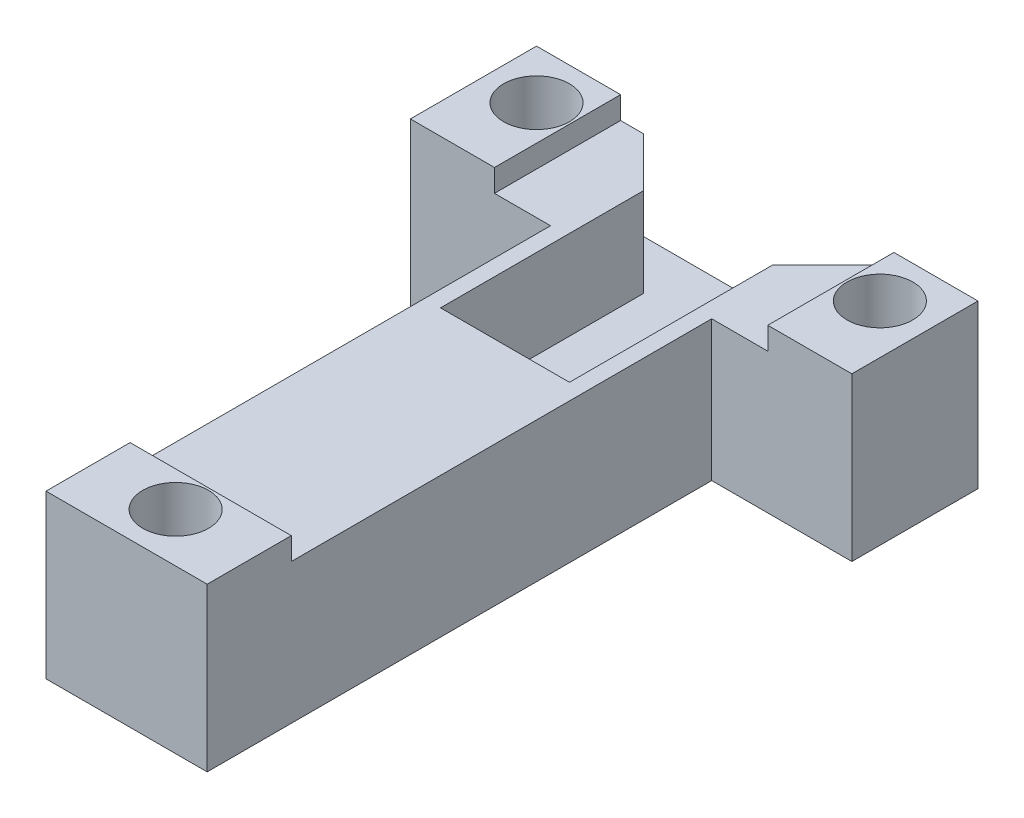
SolidWorks part; units mm, degrees
ref_plane "Front Plane" through (0, 0, 0) normal (0, 0, 1) x (1, 0, 0)
ref_plane "Top Plane" through (0, 0, 0) normal (0, 1, 0) x (1, 0, 0)
ref_plane "Right Plane" through (0, 0, 0) normal (1, 0, 0) x (0, 0, -1)
sketch "Sketch1" plane through (0, 0, 0) normal (0, 1, 0) x (1, 0, 0)
  line L0 (11.5, 45) -> (21.5, 45)
  line L1 (0, 0) -> (11.5, 0)
  line L2 (0, 0) -> (0, 45)
  line L3 (0, 45) -> (11.5, 45)
  line L4 (11.5, 0) -> (11.5, 45)
  line L5 (21.5, 45) -> (21.5, 36)
  line L6 (21.5, 36) -> (11.5, 36)
  line L7 (0, 45) -> (-10, 45)
  line L8 (-10, 45) -> (-10, 36)
  line L9 (-10, 36) -> (0, 36)
  dimension "D3" = 9
  dimension "D1" = 45
  dimension "D2" = 11.5
  dimension "D4" = 10
  dimension "D5" = 10
extrude "Boss-Extrude1" add sketch "Sketch1" along normal blind 10 contours L8 L9 L2 L7 | L6 L5 L0 L4 | L4 L3 L2 L1 region at (16.5, 0, -40.5) region at (-5, 0, -40.5)
sketch "Sketch2" plane through (0, 10, 0) normal (0, 1, 0) x (1, 0, 0)
  line L0 (5.75, 0) -> (5.75, 45) construction
  line L3 (0, 36) -> (11.5, 36) construction
  line L4 (5.75, 36) -> (5.75, 27)
  line L5 (1.15, 27) -> (10.35, 27)
  line L6 (1.15, 27) -> (1.15, 45)
  line L7 (21.5, 45) -> (-10, 45) construction
  line L8 (10.35, 27) -> (10.35, 45)
  line L9 (1.15, 45) -> (10.35, 45)
  line L10 (0, 0) -> (11.5, 0) construction
  line L11 (-10, 45) -> (-10, 36) construction
  line L12 (21.5, 45) -> (21.5, 36) construction
  line L13 (1.15, 41.5) -> (-2.35, 45)
  line L14 (10.35, 41.5) -> (13.85, 45)
  circle A0 centre (5.75, 3.5) radius 2.3495
  circle A1 centre (-6.5, 41.5) radius 2.3495
  circle A2 centre (18, 41.5) radius 2.3495
  point P17 (5.75, 27)
  line M29 (21.5, 45) -> (-10, 45)
  dimension "D1" = 4.699
  dimension "D9" = 4.699
  dimension "D10" = 4.699
  dimension "D2" = 9
  dimension "D3" = 9.2
  dimension "D4" = 3.5
  dimension "D5" = 3.5
  dimension "D6" = 3.5
  dimension "D7" = 3.5
  dimension "D8" = 3.5
  dimension "D11" = 3.5
  dimension "D12" = 3.5
  dimension "D13" = 3.5
  dimension "D14" = 3.5
extrude "Cut-Extrude1" cut sketch "Sketch2" against normal blind 6.35 contours A0 | A2 | L9 L6 L5 L8 | A1 | L13 L6 M29 | L8 L14 M29 region at (1.3521, 10, -34.25) region at (-0.0167, 10, -43.8333) region at (11.5167, 10, -43.8333) region at (5.75, 10, -3.5) region at (-6.5, 10, -41.5) region at (18, 10, -41.5)
sketch "Sketch3" plane through (0, 0, 0) normal (0, -1, 0) x (1, 0, 0)
  line L0 (5.75, 0) -> (5.75, -45) construction
  line L1 (0, 0) -> (11.5, 0) construction
  line L2 (21.5, -45) -> (-10, -45) construction
  circle A0 centre (5.75, -10) radius 2.3495
  circle A1 centre (5.75, -22) radius 2.3495
  dimension "D3" = 4.699
  dimension "D4" = 4.699
  dimension "D1" = 10
  dimension "D2" = 12
extrude "Cut-Extrude2" cut sketch "Sketch3" against normal blind 6.35
sketch "Sketch4" plane through (0, 10, 0) normal (0, 1, 0) x (1, 0, 0)
  line L0 (-4, 36) -> (-4, 45)
  line L1 (-10, 36) -> (0, 36) construction
  line L2 (-2.35, 45) -> (-10, 45) construction
  line L3 (15.5, 36) -> (15.5, 45)
  line L4 (21.5, 36) -> (11.5, 36) construction
  line L5 (21.5, 45) -> (13.85, 45) construction
  line L6 (0, 6) -> (11.5, 6)
  line L7 (0, 0) -> (0, 36) construction
  line L8 (11.5, 0) -> (11.5, 36) construction
  line L9 (0, 0) -> (11.5, 0) construction
  line L10 (-10, 45) -> (-10, 36) construction
  line L11 (21.5, 45) -> (21.5, 36) construction
  circle M4 centre (5.75, 3.5) radius 2.3495
  circle M5 centre (-6.5, 41.5) radius 2.3495
  circle M6 centre (18, 41.5) radius 2.3495
  line M9 (-2.35, 45) -> (-10, 45)
  line M10 (-10, 45) -> (-10, 36)
  line M11 (-10, 36) -> (0, 36)
  line M12 (0, 36) -> (0, 0)
  line M13 (0, 0) -> (11.5, 0)
  line M14 (11.5, 0) -> (11.5, 36)
  line M15 (11.5, 36) -> (21.5, 36)
  line M16 (21.5, 36) -> (21.5, 45)
  line M17 (21.5, 45) -> (13.85, 45)
  dimension "D1" = 6
  dimension "D2" = 6
  dimension "D3" = 6
extrude "Boss-Extrude2" add sketch "Sketch4" along normal blind 1.6 contours L0 M11 M9 M10 M5 | L3 M15 M16 M17 M6 | L6 M12 M13 M14 M4 region at (-7, 10, -36.1082) region at (15.6082, 10, -40.5) region at (5.75, 10, -5.8703)
